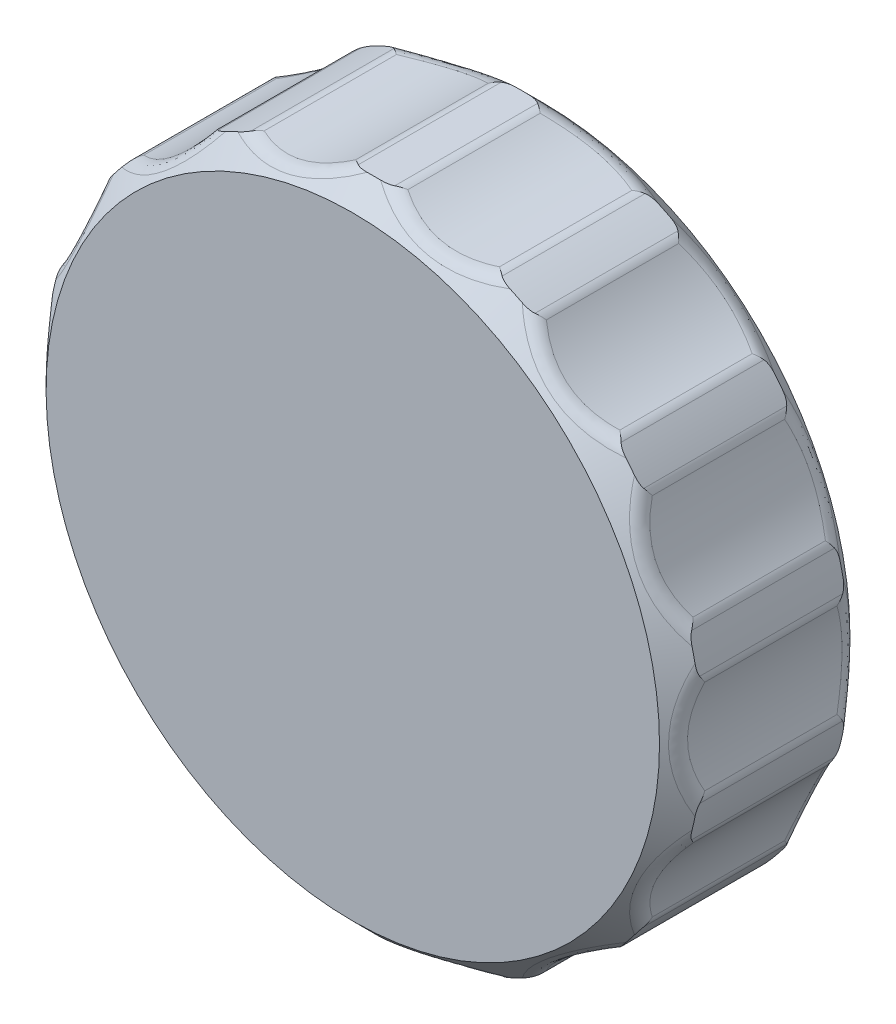
SolidWorks part; units mm, degrees
note: '?' marks a value the reader was unsure of. The reader was unsure of these and kept them because the rebuilt part matched: shared geometry of "Sketch1<6>", "Sketch1<7>", "Sketch3<3>", "Sketch2<2>".
ref_plane "Front Plane" through (0, 0, 0) normal (0, 0, 1) x (1, 0, 0)
ref_plane "Top Plane" through (0, 0, 0) normal (0, 1, 0) x (1, 0, 0)
ref_plane "Right Plane" through (0, 0, 0) normal (1, 0, 0) x (0, 0, -1)
sketch "Sketch1" plane through (0, 0, 0) normal (0, 0, 1) x (1, 0, 0)
  circle A1 centre (0, 0) radius 13.15
  circle A3 centre (0, 0) radius 11.15
  circle A5 centre (0, 0) radius 3.15
  circle A7 centre (0, 0) radius 2.15
  circle A11 centre (0, 0) radius 4.025
  dimension "D1" = 8.05
  dimension "D2" = 26.3
  dimension "D3" = 22.3
  dimension "D4" = 6.3
  dimension "D5" = 4.3
extrude "Boss-Extrude3" add sketch "Sketch1" against normal blind 11 contours A5 A7
extrude "Boss-Extrude4" add sketch "Sketch1<6>" against normal blind 9 contours A7
sketch "Sketch1<6>" plane through (0, 0, 0) normal (0, 0, 1) x (1, 0, 0) same geometry as "Sketch1"
extrude "Boss-Extrude5" add sketch "Sketch1<7>" against normal blind 11 contours A11 A5
sketch "Sketch1<7>" plane through (0, 0, 0) normal (0, 0, 1) x (1, 0, 0) same geometry as "Sketch1"
chamfer "Chamfer1" distance 0.5 angle 45 2 edges at (2.15, 0, -11) (4.025, 0, -11)
sketch "Sketch2" plane through (0, 0, 0) normal (0, 0, 1) x (1, 0, 0)
  circle A5 centre (0, 0) radius 4.025
  circle A6 centre (0, 0) radius 4.025
  dimension "D1" = 0
extrude "Boss-Extrude6" add sketch "Sketch2" along normal blind 2
sketch "Sketch3" plane through (0, 0, 2) normal (0, 0, 1) x (1, 0, 0)
  circle A0 centre (0, 0) radius 15.5
  circle A1 centre (0, 0) radius 13.5
  circle M2 centre (0, 0) radius 4.025
  dimension "D1" = 2
  dimension "D2" = 27
extrude "Boss-Extrude7" add sketch "Sketch3" along normal blind 2 separate body contours A1 M2 | A0 A1 | M2
extrude "Boss-Extrude8" add sketch "Sketch3<3>" against normal blind 7
sketch "Sketch3<3>" plane through (0, 0, 2) normal (0, 0, 1) x (1, 0, 0) same geometry as "Sketch3"
chamfer "Chamfer2" distance 1 angle 45 2 edges at (15.5, 0, -5) (15.5, 0, 4)
extrude "Boss-Extrude9" add sketch "Sketch2<2>" along normal up to surface (4 mm away) up to face at (14.5, 0, 4)
sketch "Sketch2<2>" plane through (0, 0, 0) normal (0, 0, 1) x (1, 0, 0) same geometry as "Sketch2"
sketch "Sketch4" plane through (0, 0, 2) normal (0, 0, -1) x (-1, 0, 0)
  circle A0 centre (0, 0) radius 6.1943
extrude "Boss-Extrude10" add sketch "Sketch4" along normal blind 0.75
sketch "Sketch7" plane through (0, 0, 4) normal (0, 0, 1) x (1, 0, 0)
  line L0 (0, 0) -> (23.7259, 0) construction
  circle A0 centre (23.7259, 0) radius 8.75
  dimension "D2" = 17.5
extrude "Cut-Extrude1" cut sketch "Sketch7" against normal through all
ref_axis "Axis1" through (0, 0, -12.7474) along (0, 0, 1)?
pattern_circular "CirPattern1" count 14 over 360 about axis through (0, 0, 0) along (0, 0, 1) of "Cut-Extrude1"
fillet "Fillet1" radius 0.9 56 edges at (13.8516, 5.8287, -4.472) (9.9509, 11.2615, -4.472) (-9.9509, -11.2615, -4.472) (-8.7648, 12.2073, -4.472) (4.0793, 14.4638, -4.472) (-2.6003, 14.8013, -4.472) (-13.1934, 7.1955, -4.472) (-15.0088, 0.7585, -4.472) (-13.8516, -5.8287, -4.472) (-4.0793, -14.4638, -4.472) (2.6003, -14.8013, -4.472) (8.7648, -12.2073, -4.472) (13.1934, -7.1955, -4.472) (14.839, 4.4783, -0.5) (12.7532, 8.8094, -0.5) (11.4264, 10.4732, -0.5) (7.668, 13.4704, -0.5) (-11.4264, -10.4732, -0.5) (-7.668, -13.4704, -0.5) (-7.668, 13.4704, -0.5) (-11.4264, 10.4732, -0.5) (5.7507, 14.3937, -0.5) (1.064, 15.4634, -0.5) (-1.064, 15.4634, -0.5) (-5.7507, 14.3937, -0.5) (-12.7532, 8.8094, -0.5) (-14.839, 4.4783, -0.5) (-15.3125, 2.4036, -0.5) (-15.3125, -2.4036, -0.5) (-14.839, -4.4783, -0.5) (-12.7532, -8.8094, -0.5) (-5.7507, -14.3937, -0.5) (-1.064, -15.4634, -0.5) (1.064, -15.4634, -0.5) (5.7507, -14.3937, -0.5) (7.668, -13.4704, -0.5) (11.4264, -10.4732, -0.5) (12.7532, -8.8094, -0.5) (14.839, -4.4783, -0.5) (15.0088, 0.7585, 3.472) (15.0088, -0.7585, -4.472) (15.3125, -2.4036, -0.5) (15.3125, 2.4036, -0.5) (13.8516, -5.8287, 3.472) (9.9509, -11.2615, 3.472) (4.0793, -14.4638, 3.472) (-2.6003, -14.8013, 3.472) (-13.1934, -7.1955, 3.472) (-15.0088, -0.7585, 3.472) (-13.8516, 5.8287, 3.472) (-4.0793, 14.4638, 3.472) (2.6003, 14.8013, 3.472) (-9.9509, 11.2615, 3.472) (-8.7648, -12.2073, 3.472) (8.7648, 12.2073, 3.472) (13.1934, 7.1955, 3.472)
